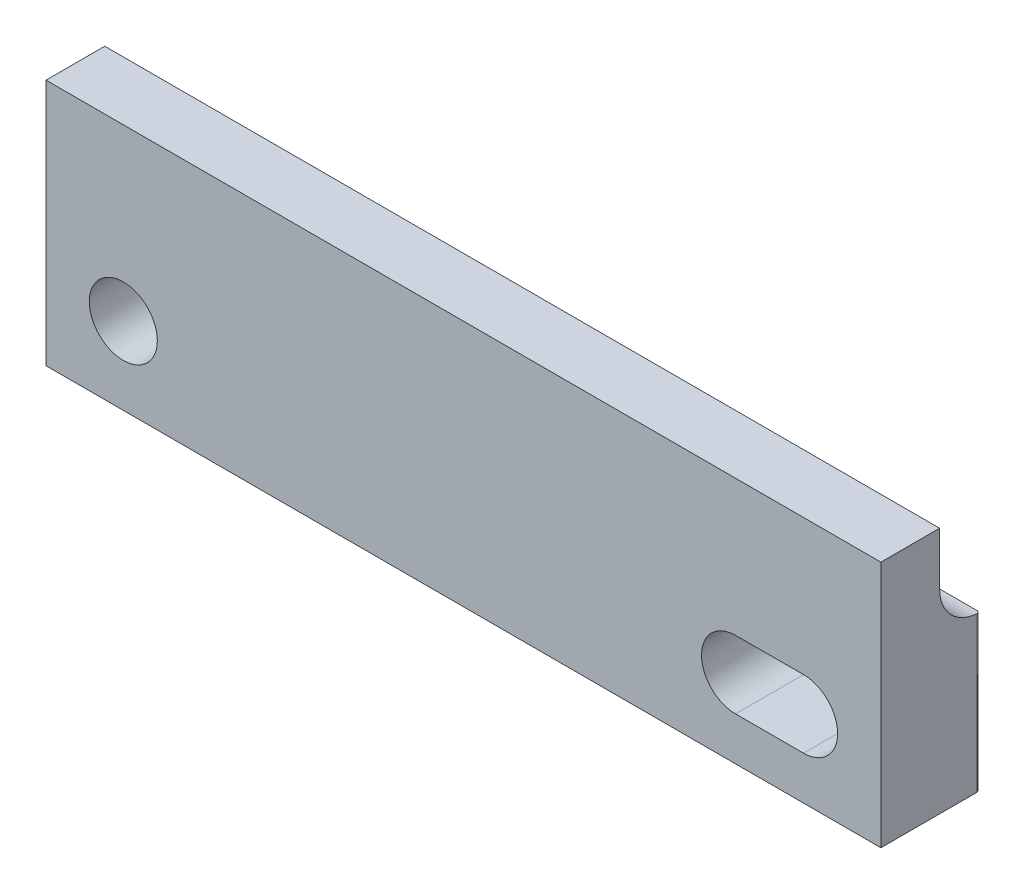
SolidWorks part; units mm, degrees
ref_plane "前视基准面" through (0, 0, 0) normal (0, 0, 1) x (1, 0, 0)
ref_plane "上视基准面" through (0, 0, 0) normal (0, 1, 0) x (1, 0, 0)
ref_plane "右视基准面" through (0, 0, 0) normal (1, 0, 0) x (0, 0, -1)
sketch "草图1" plane through (0, 0, 0) normal (0, 0, 1) x (1, 0, 0)
  line L1 (0, 0) -> (270, 0)
  line L2 (0, 0) -> (0, 80)
  line L3 (0, 80) -> (270, 80)
  line L4 (270, 0) -> (270, 80)
  dimension "D1" = 270
  dimension "D2" = 80
extrude "拉伸1" add sketch "草图1" along normal blind 32
sketch "草图2" plane through (0, 0, 32) normal (0, 0, 1) x (1, 0, 0)
  line L0 (0, 80) -> (0, 0) construction
  line L1 (0, 0) -> (270, 0) construction
  line L2 (245, -928.2855) -> (245, 49071.7145) construction
  line L3 (223, -932.4386) -> (223, 49067.5614) construction
  line L4 (270, 0) -> (270, 80) construction
  line L5 (-977.8887, 25) -> (49022.1113, 25) construction
  line L6 (223, 36) -> (245, 36)
  line L7 (223, 14) -> (245, 14)
  circle A0 centre (25, 25) radius 11
  arc A1 (223, 14) -> (223, 36) centre (223, 25) cw
  arc A2 (245, 36) -> (245, 14) centre (245, 25) cw
  dimension "D1" = 25
  dimension "D2" = 25
  dimension "D3" = 25
  dimension "D4" = 22
extrude "切除-拉伸1" cut sketch "草图2" against normal through all
sketch "草图3" plane through (0, 0, 0) normal (-1, 0, 0) x (0, 0, 1)
  line L0 (13, 80) -> (13, 63)
  line L1 (0, 80) -> (0, 0) construction
  line L3 (32, 80) -> (0, 80) construction
  line L4 (13, 80) -> (0, 80)
  line L5 (0, 80) -> (0, 50)
  arc A0 (13, 63) -> (0, 50) centre (0, 63) cw
  point P4 (0, 63)
  dimension "D1" = 17
  dimension "D2" = 13
  dimension "D3" = 13
extrude "切除-拉伸2" cut sketch "草图3" against normal through all
fillet "圆角1" radius 1 1 edges at (270, 25, 0)
fillet "圆角2" radius 1 1 edges at (0, 25, 0)
fillet "圆角4" radius 1 1 edges at (135, 0, 0)
